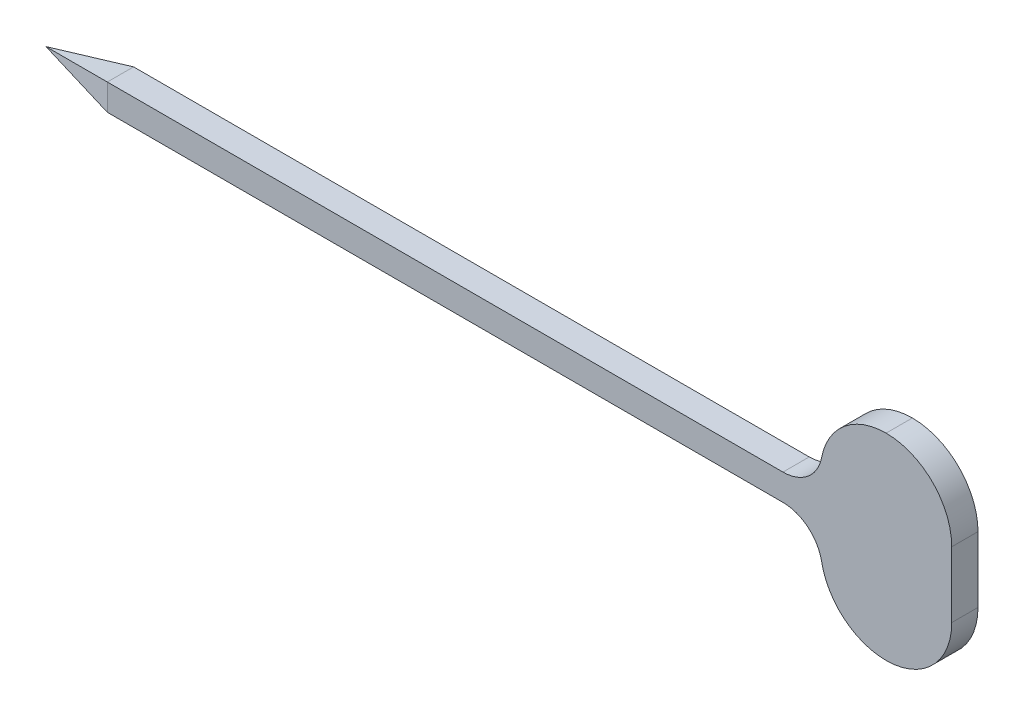
SolidWorks part; units mm, degrees
ref_plane "Front Plane" through (0, 0, 0) normal (0, 0, 1) x (1, 0, 0)
ref_plane "Top Plane" through (0, 0, 0) normal (0, 1, 0) x (1, 0, 0)
ref_plane "Right Plane" through (0, 0, 0) normal (1, 0, 0) x (0, 0, -1)
sketch "Sketch1" plane through (0, 0, 0) normal (0, 0, 1) x (1, 0, 0)
  line L1 (30, -1) -> (-30, -1)
  line L2 (30, -1) -> (30, 1)
  line L3 (30, 1) -> (-30, 1)
  line L4 (-30, -1) -> (-30, 1)
  line L5 (30, -1) -> (-30, 1) construction
  line L6 (30, 1) -> (-30, -1) construction
  line L7 (30, 7.5) -> (40, 7.5)
  line L8 (30, 7.5) -> (30, -7.5)
  line L9 (30, -7.5) -> (40, -7.5)
  line L10 (40, 7.5) -> (40, -7.5)
  point P0 (0, 0)
  point P10 (40, 0)
  point P11 (-30, 0)
  dimension "D1" = 2
  dimension "D2" = 60
  dimension "D3" = 10
  dimension "D4" = 15
extrude "Boss-Extrude1" add sketch "Sketch1" along normal blind 2 contours L4 L1 L2 L3 | L10 L7 L8 L2 L9 region at (0, 0, 0) region at (35, 0, 0)
chamfer "Chamfer1" distance 1 angle 80 4 edges at (-30, 1, 1) (-30, 0, 2) (-30, -1, 1) (-30, 0, 0) first distance on face at (-30, 0, 1)
fillet "Fillet1" radius 5 4 edges at (40, -7.5, 1) (40, 7.5, 1) (30, 7.5, 1) (30, -7.5, 1)
fillet "Fillet2" radius 3 2 edges at (30, 1, 1) (30, -1, 1)
